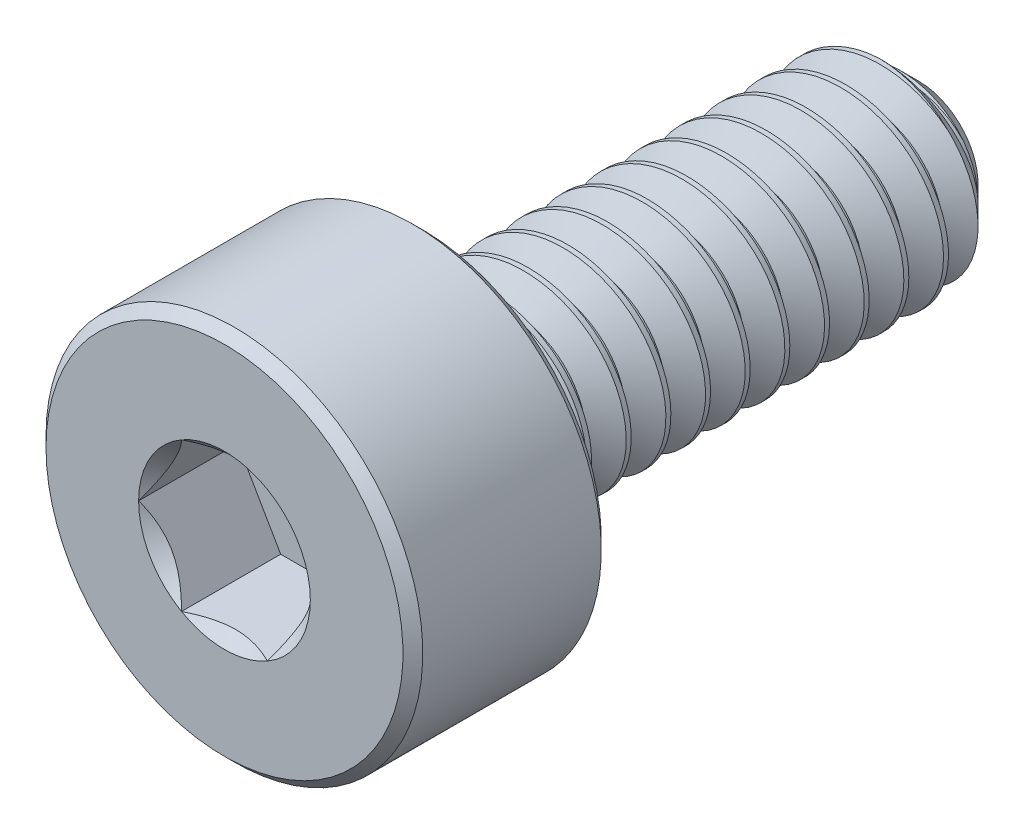
SolidWorks part; units mm, degrees
ref_plane "Front Plane" through (0, 0, 0) normal (0, 0, 1) x (1, 0, 0)
ref_plane "Top Plane" through (0, 0, 0) normal (0, 1, 0) x (1, 0, 0)
ref_plane "Right Plane" through (0, 0, 0) normal (1, 0, 0) x (0, 0, -1)
sketch "Sketch1" plane through (0, 0, 0) normal (1, 0, 0) x (0, 0, -1)
  line L0 (-3.5, 0) -> (3.5, 0) construction
  line L1 (3.5, 0) -> (3.5, 0.6) construction
  line L2 (3.5, 0.6) -> (3.1, 1) construction
  line L3 (3.1, 1) -> (2.1, 1) construction
  line L4 (2.1, 1) -> (-1.5, 1) construction
  line L5 (-1.5, 1) -> (-1.5, 1.9) construction
  line L6 (-1.5, 1.9) -> (-3.5, 1.9) construction
  line L7 (-3.5, 1.9) -> (-3.5, 0) construction
  line L8 (3.5, 0.6) -> (3.5, 1) construction
  line L9 (3.475, 1.0433) -> (3.675, 0.6969) construction
  line L10 (3.675, 0.6969) -> (3.875, 1.0433) construction
  line L11 (3.875, 1.0433) -> (3.475, 1.0433) construction
  line L12 (3.675, 1.0433) -> (3.675, 1) construction
  line L13 (3.675, 0.6969) -> (3.675, 0.7402) construction
  line L14 (3.65, 0.7402) -> (3.7, 0.7402) construction
  line L15 (3.5, 1) -> (3.85, 1) construction
  line L16 (3.4875, 1.0217) -> (3.8625, 1.0217) construction
  line L17 (3.5, 0) -> (3.5, -1) construction
  line L18 (-1.6, 1.9) -> (-1.5, 1.8) construction
  line L19 (-3.4, 1.9) -> (-3.5, 1.8) construction
  point P0 (-3.5, 0.75)
  point P3 (2.1, 1)
  point P4 (0, 0)
  point P18 (1.1, 1)
  point P22 (3.675, 0.7402)
  point P24 (2.1, 1)
  point P25 (3.675, 1)
  point P28 (3.675, 1.0217)
  point P29 (2.1, -1)
  point P30 (-0.5, 1)
  point P31 (-2.5, 1.9)
  point P37 (-1.85, 1.9)
  point P38 (-3.35, 1.9)
  dimension "head height" = 2
  dimension "D1" = 45
  dimension "head dia" = 3.8
  dimension "thread dia" = 2
  dimension "drive size" = 1.5
  dimension "pitch" = 0.4
  dimension "D2" = 0.05
  dimension "D3" = 0.4
  dimension "D4" = 1.4
  dimension "D5" = 1
  dimension "D6" = 1
  dimension "D7" = 0.1
  dimension "D8" = 0.1
  dimension "D9" = 0.1
  dimension "D10" = 0.05
  dimension "D11" = 0.25
  dimension "length" = 5
sketch "Sketch2" plane through (0, 0, 0) normal (1, 0, 0) x (0, 0, -1)
  line L0 (-3.5, 0) -> (-3.5, 1.8)
  line L1 (-3.4, 1.9) -> (-1.6, 1.9)
  line L2 (-1.5, 1.8) -> (-1.5, 1)
  line L3 (-1.5, 1) -> (3.1, 1)
  line L4 (3.1, 1) -> (3.5, 0.6)
  line L5 (3.5, 0.6) -> (3.5, 0)
  line L6 (-1.6, 1.9) -> (-1.5, 1.8) construction
  line L7 (3.5, 0) -> (-3.5, 0)
  line L8 (-3.4, 1.9) -> (-3.5, 1.8) construction
  line L9 (-1.6, 1.9) -> (-1.5, 1.8)
  line L10 (-3.4, 1.9) -> (-3.5, 1.8)
revolve "Revolve1" add sketch "Sketch2" angle 360 about L7
sketch "Sketch3" plane through (0, 0, 3.5) normal (0, 0, 1) x (1, 0, 0)
  line L1 (0.433, 0.75) -> (-0.433, 0.75)
  line L2 (-0.433, 0.75) -> (-0.866, 0)
  line L3 (-0.866, 0) -> (-0.433, -0.75)
  line L4 (-0.433, -0.75) -> (0.433, -0.75)
  line L5 (0.433, -0.75) -> (0.866, 0)
  line L6 (0.866, 0) -> (0.433, 0.75)
  circle A0 centre (0, 0) radius 0.75 construction
extrude "Cut-Extrude1" cut sketch "Sketch3" against normal offset from surface (1 mm away) 1 up to face at (-1.8, 0, 1.5)
sketch "Sketch4" plane through (0, 0, 3.5) normal (0, 0, 1) x (1, 0, 0)
  circle A0 centre (0, 0) radius 0.866
extrude "Cut-Extrude2" cut sketch "Sketch4" against normal up to vertex (1 mm away) draft 45 up to point (0, 1.9, 2.5)
ref_plane "Plane1" through (0, 0, -2.1) normal (0, 0, 1) x (1, 0, 0)
split "Split1" bodies to split 106 resulting bodies 107 108 split by face at (-1.8, 0, 1.5)
sketch "Sketch6" plane through (0, 0, -3.5) normal (0, 0, -1) x (-1, 0, 0)
  circle A0 centre (0, 0) radius 1
curve "Helix/Spiral1" pitch 0.4 height 5.4 radius 1 centre (0, 0, -3.5) axis (0, 0, 1) start towards (0, 1, 0)
sketch "Sketch7" plane through (0, 0, 0) normal (1, 0, 0) x (0, 0, -1)
  line L0 (3.4875, 1.0217) -> (3.8625, 1.0217)
  line L1 (3.8625, 1.0217) -> (3.7, 0.7402)
  line L2 (3.7, 0.7402) -> (3.65, 0.7402)
  line L3 (3.65, 0.7402) -> (3.4875, 1.0217)
sweep "Cut-Sweep1" cut profiles "Sketch7" path "Helix/Spiral1" align with end faces yes
sketch "Sketch8" plane through (0, 0, 1.5) normal (0, 0, -1) x (-1, 0, 0)
  circle A0 centre (0, 0) radius 1
extrude "Boss-Extrude1" add sketch "Sketch8" along normal through all draft 70.5
equation "\"D2@Sketch1\"=\"pitch@Sketch1\"/8"
equation "\"D3@Sketch1\"=\"pitch@Sketch1\""
equation "\"D3@Helix/Spiral1\"=\"length@Sketch1\"+\"pitch@Sketch1\""
equation "\"D4@Helix/Spiral1\"=\"pitch@Sketch1\""
equation "\"D4@Sketch1\"=\"pitch@Sketch1\"*3.5"
equation "\"D7@Sketch1\"=\"head height@Sketch1\"*.05"
equation "\"D8@Sketch1\"=\"D7@Sketch1\""
equation "\"D9@Sketch1\"=\"D7@Sketch1\""
equation "\"D10@Sketch1\"=\"D7@Sketch1\"/2"
equation "\"D11@Sketch1\"=\"D10@Sketch1\"*5"
